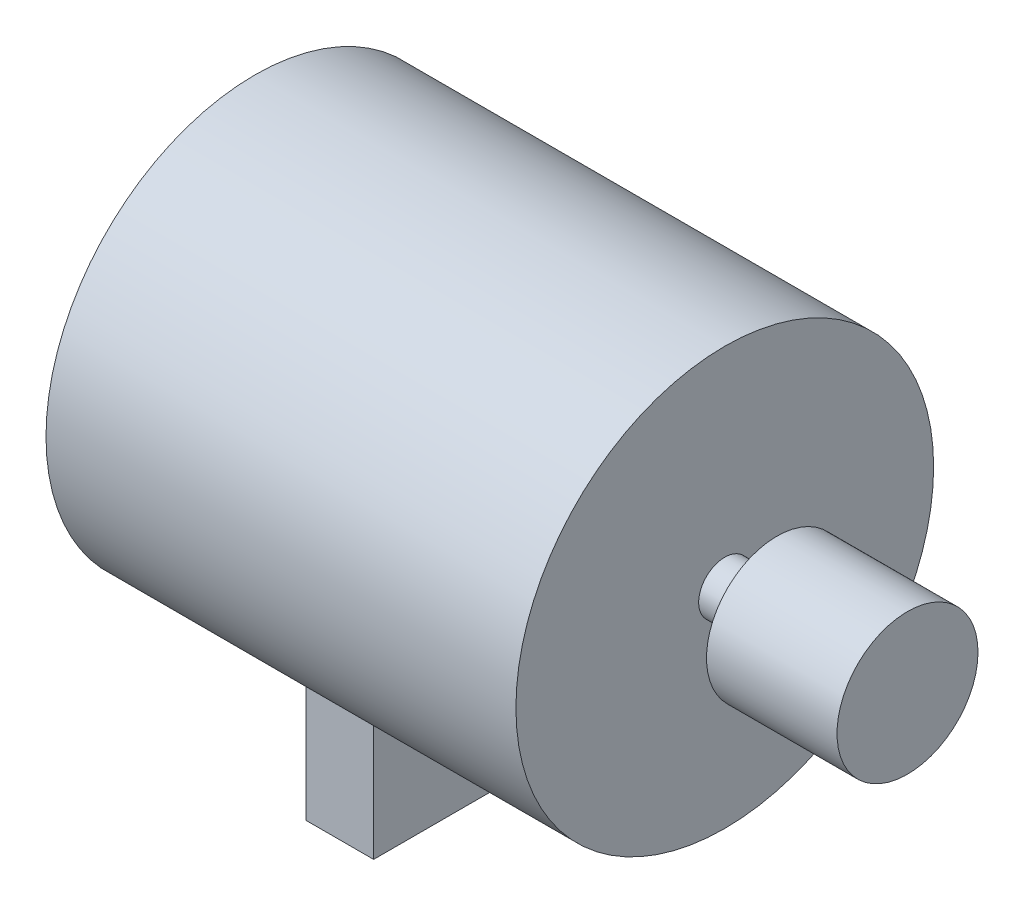
SolidWorks part; units mm, degrees
ref_plane "Front Plane" through (0, 0, 0) normal (0, 0, 1) x (1, 0, 0)
ref_plane "Top Plane" through (0, 0, 0) normal (0, 1, 0) x (1, 0, 0)
ref_plane "Right Plane" through (0, 0, 0) normal (1, 0, 0) x (0, 0, -1)
sketch "Sketch4" plane through (0, 0, 0) normal (0, 0, 1) x (1, 0, 0)
  line L0 (-4.5, 0) -> (4.5, 0)
  line L1 (4.5, 0) -> (4.5, 4)
  line L2 (-4.5, 0) -> (-4.5, 4)
  line L3 (-4.5, 4) -> (4.5, 4)
  dimension "D1" = 4
  dimension "D2" = 9
revolve "Revolve3" add sketch "Sketch4" angle 360 about L3
sketch "Sketch5" plane through (0, 0, 0) normal (0, 1, 0) x (1, 0, 0)
  line L1 (-0.65, -2.875) -> (0.65, -2.875)
  line L2 (-0.65, -2.875) -> (-0.65, 2.875)
  line L3 (-0.65, 2.875) -> (0.65, 2.875)
  line L4 (0.65, -2.875) -> (0.65, 2.875)
  line L5 (-0.65, -2.875) -> (0.65, 2.875) construction
  line L6 (-0.65, 2.875) -> (0.65, -2.875) construction
  point P0 (0, 0)
  dimension "D1" = 5.75
  dimension "D2" = 1.3
extrude "Boss-Extrude1" add sketch "Sketch5" along normal up to surface and the other way blind 1 up to face at (4.5, 4, 4)
sketch "Sketch6" plane through (4.5, 0, 0) normal (1, 0, 0) x (0, 0, -1)
  circle A0 centre (0, 4) radius 0.5
  dimension "D1" = 1
extrude "Boss-Extrude2" add sketch "Sketch6" along normal blind 3.5
sketch "Sketch7" plane through (8, 0, 0) normal (1, 0, 0) x (0, 0, -1)
  circle A0 centre (0, 4) radius 1.35
  dimension "D1" = 2.7
extrude "Boss-Extrude3" add sketch "Sketch7" against normal blind 2.5
